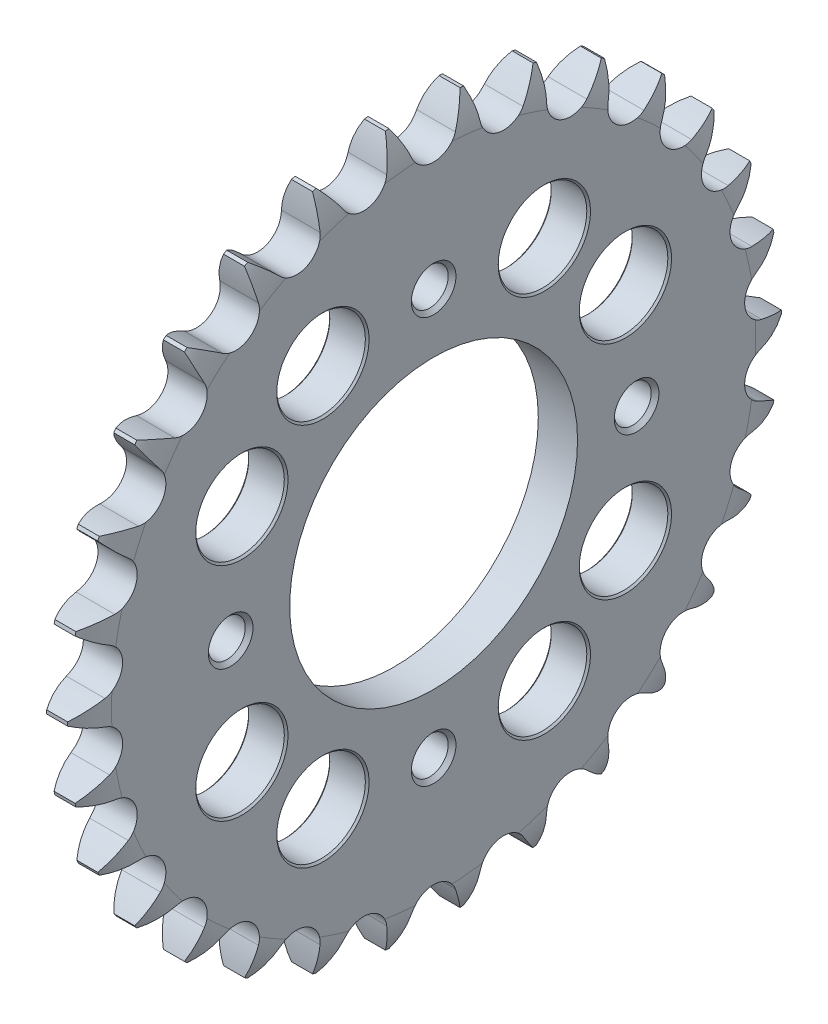
SolidWorks part; units mm, degrees
material "1.0503 (C45)"
ref_plane "Plane1" through (0, 0, 0) normal (0, 0, 1) x (1, 0, 0)
ref_plane "Plane2" through (0, 0, 0) normal (0, 1, 0) x (1, 0, 0)
ref_plane "Plane3" through (0, 0, 0) normal (1, 0, 0) x (0, 0, -1)
sketch "Clipboard" plane through (0, 0, 0) normal (0, 1, 0) x (1, 0, 0)
  line L0 (0, 0) -> (8.2489, -4.7625)
  line L1 (-15, 0) -> (100, 0) construction
  line L2 (0, 0) -> (-0.8203, 0.9272)
  line L3 (0, 0) -> (-8.8973, 3.4006)
  line L4 (0, 0) -> (2.6847, 1.55)
  line L5 (0, 0) -> (-46.8476, -17.4728)
  line L6 (0, 0) -> (-4.4098, -2.9753)
  line L7 (-0.8203, 0.9272) -> (42.0384, 26.6793)
  line L8 (-76.2, 38.1) -> (-75.5, 38.1)
  line L9 (-73.3242, 40.7328) -> (-72.926, 40.7699)
  line L10 (-73.4529, 9.1872) -> (-63.2129, 9.1872)
  circle A0 centre (0, 0) radius 3.175
  circle A1 centre (0, 0) radius 37.5
  circle A2 centre (0, 0) radius 37.5
  dimension "Dr" = 6.35
  dimension "MHD" = 75
  dimension "Hub_dia" = 75
  dimension "Num_teeth" = 30
  dimension "Pitch" = 9.525
  dimension "Width" = 3.1
  dimension "Side_relief" = 1.238
  dimension "Side_radius" = 9.525
  dimension "Overall_len" = 50
  dimension "Show_teeth" = 30
  dimension "Thickness" = 5.3196
  dimension "OAL" = 50.0005
  dimension "T_dim" = 0.7
  dimension "Fillet_rad" = 0.4
  dimension "Face_width" = 5.32
  dimension "Num_strands" = 1
  dimension "Transv_pitch" = 10.24
  dimension "Plate_wid" = 8.26
sketch "BasProSke" plane through (0, 0, 0) normal (0, 1, 0) x (1, 0, 0)
  line L0 (-10, 0) -> (60, 0) construction
  line L1 (0, 0) -> (0, 43.644)
  line L2 (0, 0) -> (5.3196, 0)
  line L3 (5.3196, 0) -> (5.3196, 43.644)
  line L4 (4.0816, 48.3399) -> (1.238, 48.3399)
  arc A0 (0, 43.644) -> (1.238, 48.3399) centre (9.525, 43.644) cw
  arc A1 (5.3196, 43.644) -> (4.0816, 48.3399) centre (-4.2054, 43.644) ccw
  dimension "Thickness" = 5.3196
  dimension "D1" = 9.525
  dimension "G1" = 1.238
  dimension "G2" = 1.238
  dimension "Diameter" = 96.6798
revolve "Base-Revolve" add sketch "BasProSke" angle 360 about L0
sketch "TooCutSke" plane through (0, 0, 0) normal (1, 0, 0) x (0, 0, -1)
  line L0 (0, 45.5935) -> (2.9836, 44.4182) construction
  line L1 (0, 0) -> (0, 107) construction
  line L2 (0, 45.5935) -> (-10, 45.5935) construction
  line L3 (0, 45.5935) -> (-2.9836, 44.4182) construction
  arc A0 (2.9836, 44.4182) -> (5.0993, 48.5729) centre (25.6709, 35.4815) cw
  arc A1 (2.9836, 44.4182) -> (-2.9836, 44.4182) centre (0, 45.5935) cw
  arc A2 (-2.9836, 44.4182) -> (-5.0993, 48.5729) centre (-25.6709, 35.4815) ccw
  arc A3 (5.0993, 48.5729) -> (-5.0993, 48.5729) centre (0, 0) ccw
  dimension "R1" = 3.2067
  dimension "R2" = 24.384
  dimension "Overcut" = 48.8399
  dimension "Seat_radius" = 45.5935
  dimension "X" = 137
extrude "ToothCut" cut sketch "TooCutSke" along normal through all
pattern_circular "TeethCuts" count 30 every 12 about axis through (-10, 0, 0) along (1, 0, 0) of "ToothCut"
sketch "HubNeaOneSke" plane through (0, 0, 0) normal (-1, 0, 0) x (0, 0, 1)
  circle A0 centre (0, 0) radius 37.5
  dimension "Diameter" = 75
extrude "HubNearOne" [suppressed] add sketch "HubNeaOneSke" along normal blind 44.6809
fillet "HubNearOneFillet" [suppressed] radius 0.4
sketch "HubNeaBotSke" plane through (0, 0, 0) normal (-1, 0, 0) x (0, 0, 1)
  circle A0 centre (0, 0) radius 37.5
  dimension "Diameter" = 75
extrude "HubNearBoth" [suppressed] add sketch "HubNeaBotSke" along normal blind 22.3405
fillet "HubNearBothFillet" [suppressed] radius 0.4
ref_plane "FarPln" through (5.3196, 0, 0) normal (1, 0, 0) x (0, 0, -1)
sketch "HubFarSke" plane through (5.3196, 0, 0) normal (1, 0, 0) x (0, 0, -1)
  circle A0 centre (0, 0) radius 37.5
  dimension "Diameter" = 75
extrude "HubFar" [suppressed] add sketch "HubFarSke" along normal blind 22.3405
fillet "HubFarFillet" [suppressed] radius 0.4
sketch "BorSke" plane through (0, 0, 0) normal (1, 0, 0) x (0, 0, -1)
  circle A0 centre (0, 0) radius 2
  dimension "Diameter" = 4
extrude "Bore" cut sketch "BorSke" along normal mid plane 100.001
sketch "KeySke" plane through (0, 0, 0) normal (1, 0, 0) x (0, 0, -1)
  line L0 (-0.8, 0) -> (-0.8, 2.7)
  line L1 (-0.8, 2.7) -> (0.8, 2.7)
  line L2 (0.8, 2.7) -> (0.8, 0)
  line L3 (0, 0) -> (0, 34) construction
  line L4 (-0.8, 0) -> (0.8, 0)
  dimension "Offset" = 2.7
  dimension "Width" = 1.6
extrude "Keyway" [suppressed] cut sketch "KeySke" along normal mid plane 100.001
pattern_circular "Keyway2" [suppressed] count 2 every 90 about axis through (-10, 0, 0) along (1, 0, 0)
sketch "Sketch1" plane through (5.3196, 0, 0) normal (1, 0, 0) x (0, 0, -1)
  circle A0 centre (0, 27.5) radius 3
  circle A1 centre (27.5, 0) radius 3
  circle A2 centre (0, -27.5) radius 3
  circle A3 centre (-27.5, 0) radius 3
  circle A4 centre (0, 0) radius 19.5
  point P11 (0, 0)
  dimension "D2" = 6
  dimension "D4" = 39
  dimension "D3" = 55
  dimension "D1" = 4
extrude "Cut-Extrude1" cut sketch "Sketch1" against normal blind 10 contours A4
hole_wizard "M6 Tapped Hole1" positions "Sketch3" profile "Sketch2" tap size "M6" standard "ISO" end condition through all
sketch "Sketch3" plane through (5.3196, 0, 0) normal (1, 0, 0) x (0, 0, -1)
  point P0 (0, 27.5)
  point P3 (-27.5, 0)
  point P6 (27.5, 0)
  point P9 (0, -27.5)
sketch "Sketch2" plane through (5.3196, 27.5, 0) normal (0, 1, 0) x (0, 0, -1)
  line L0 (0, 0) -> (0, 5.3196)
  line L1 (0, 5.3196) -> (2.5, 5.3196)
  line L2 (2.5, 5.3196) -> (2.5, 0.525)
  line L3 (2.5, 0.525) -> (3.025, 0)
  line L5 (3.025, 0) -> (0, 0)
  line L6 (-2.5, 0.525) -> (-3.025, 0) construction
  line L11 (0, -6.35) -> (0, 107.95) construction
  dimension "Thread Major Dia." = 5
  dimension "Thru Tap Drill Depth" = 5.3196
  dimension "Near C'Sink Dia." = 6.05
  dimension "Near C'Sink Angle" = 90
hole_wizard "Ø12.0 (12) Diameter Hole1" positions "Sketch7" profile "Sketch6" hole size "Ø12.0" standard "ISO" end condition through all
sketch "Sketch7" plane through (5.3196, 0, 0) normal (1, 0, 0) x (0, 0, -1)
  line L0 (0, 27.5) -> (0, 0) construction
  line L1 (0, 0) -> (15, 25.9808) construction
  point P0 (15, 25.9808)
  dimension "D1" = 30
  dimension "D2" = 30
sketch "Sketch6" plane through (5.3196, 25.9808, -15) normal (0, 1, 0) x (0, 0, -1)
  line L0 (0, 0) -> (0, 5.3196)
  line L1 (0, 5.3196) -> (6, 5.3196)
  line L2 (6, 5.3196) -> (6, 0)
  line L5 (6, 0) -> (0, 0)
  line L11 (0, -6.35) -> (0, 107.95) construction
  dimension "Thru Hole Dia." = 12
  dimension "Thru Hole Depth" = 5.3196
chamfer "Chamfer1" distance 0.25 angle 45 2 edges at (5.3196, 25.9808, -21) (0, 25.9808, -21)
pattern_circular "CirPattern1" count 12 over 360 about axis through (-4.6804, 0, 0) along (1, 0, 0) of "Ø12.0 (12) Diameter Hole1", "Chamfer1"
equation "' \"Pitch@Clipboard\" = 12.7"
equation "' \"Num_strands@Clipboard\" = 1"
equation "' \"Num_teeth@Clipboard\" = 9"
equation "' \"Hub_dia@Clipboard\" = 50"
equation "' \"Overall_len@Clipboard\" = 3"
equation "' \"Diameter@BorSke\" = 12"
equation "' \"T_dim@Clipboard\" = 1"
equation "' \"Width@KeySke\" = 2"
equation "' \"Dr@Clipboard\" = 8.51"
equation "' \"Face_width@Clipboard\" = 7.2"
equation "' \"Side_radius@Clipboard\" = 12.7"
equation "' \"Side_relief@Clipboard\" = 1.27"
equation "' \"Transv_pitch@Clipboard\" = 13.92"
equation "' \"Show_teeth@Clipboard\" = 9"
equation "' \"Fillet_rad@Clipboard\" = 0.6"
equation "' \"Plate_wid@Clipboard\" = 11.8"
equation "\"Num_teeth@Clipboard\" = int( \"Num_teeth@Clipboard\" )"
equation "\"Num_teeth@Clipboard\" = ((sgn( \"Num_teeth@Clipboard\" - 5.0)+1)*( \"Num_teeth@Clipboard\" - 5.0))/2 +5.0"
equation "\"Num_teeth@Clipboard\" = ((sgn( \"Num_teeth@Clipboard\" - 200.0)-1)*( \"Num_teeth@Clipboard\" - 200.0))/-2 +200.0"
equation "\"MHD@Clipboard\" = \"Pitch@Clipboard\" * (1.0 / tan(3.14159265 / \"Num_teeth@Clipboard\" )) - 1.04 * \"Plate_wid@Clipboard\" - 0.76"
equation "\"Thickness@Clipboard\"  = \"Face_width@Clipboard\" + (\"Num_strands@Clipboard\" - 1) * \"Transv_pitch@Clipboard\""
equation "\"OAL@Clipboard\" = \"Thickness@Clipboard\" + 2 * \"Fillet_rad@Clipboard\" + 1"
equation "\"MHD@Clipboard\" = ((sgn( \"MHD@Clipboard\" - \"Hub_dia@Clipboard\" )-1)*( \"MHD@Clipboard\" - \"Hub_dia@Clipboard\" ))/-2+ \"Hub_dia@Clipboard\""
equation "\"OAL@Clipboard\" = ((sgn( \"OAL@Clipboard\" - \"Overall_len@Clipboard\" )+1)*( \"OAL@Clipboard\" - \"Overall_len@Clipboard\" ))/2 + \"Overall_len@Clipboard\" + 0.0005"
equation "\"Num_teeth@TeethCuts\" = int( \"Show_teeth@Clipboard\" ) + 1"
equation "\"Num_teeth@TeethCuts\" = ((sgn( \"Num_teeth@TeethCuts\" - \"Num_teeth@Clipboard\" )-1)*( \"Num_teeth@TeethCuts\" - \"Num_teeth@Clipboard\" ))/-2+ \"Num_teeth@Clipboard\""
equation "\"Num_teeth@TeethCuts\" = ((sgn( \"Num_teeth@TeethCuts\" - 2.0)+1)*( \"Num_teeth@TeethCuts\" - 2.0))/2 +2.0"
equation "\"Angle@TeethCuts\" = 360.0 / \"Num_teeth@Clipboard\""
equation "\"Seat_radius@TooCutSke\" = ( \"Pitch@Clipboard\" / 2.0) / sin(3.14159265 / \"Num_teeth@Clipboard\" ) - \"Dr@Clipboard\" / 2.0 + \"Dr@Clipboard\" * 0.505"
equation "\"R1@TooCutSke\"  = \"Dr@Clipboard\" * 0.505"
equation "\"X@TooCutSke\" = 140.0 - (90.0 / \"Num_teeth@Clipboard\")"
equation "\"R2@TooCutSke\" = 0.12 * \"Dr@Clipboard\" * ( \"Num_teeth@Clipboard\" + 2.0)"
equation "\"Overcut@TooCutSke\" = 0.5 + 0.625 * \"Pitch@Clipboard\" - 0.5 * \"Dr@Clipboard\"  +  \"Pitch@Clipboard\" / 2.0 / sin(3.14159265 / \"Num_teeth@Clipboard\" )"
equation "\"Diameter@BasProSke\" = 2.0 * ( 0.625 * \"Pitch@Clipboard\" - 0.5 * \"Dr@Clipboard\"  +  \"Pitch@Clipboard\" / 2.0 / sin(3.14159265 / \"Num_teeth@Clipboard\" ))"
equation "\"Thickness@BasProSke\"  = \"Thickness@Clipboard\""
equation "\"G1@BasProSke\" =  \"Side_relief@Clipboard\""
equation "\"G2@BasProSke\" =  \"Side_relief@Clipboard\""
equation "\"D1@BasProSke\" =  \"Side_radius@Clipboard\""
equation "\"Diameter@HubNeaOneSke\" = \"MHD@Clipboard\""
equation "\"Length@HubNearOne\" = \"OAL@Clipboard\" - \"Thickness@BasProSke\""
equation "\"Diameter@HubNeaBotSke\" = \"MHD@Clipboard\""
equation "\"Length@HubNearBoth\" = ( \"OAL@Clipboard\" - \"Thickness@BasProSke\" ) / 2.0"
equation "\"D1@HubNearOneFillet\" = \"Fillet_rad@Clipboard\""
equation "\"D1@HubNearBothFillet\" = \"Fillet_rad@Clipboard\""
equation "\"Thickness@FarPln\" = \"Thickness@BasProSke\""
equation "\"Diameter@HubFarSke\" = \"MHD@Clipboard\""
equation "\"Length@HubFar\" = ( \"OAL@Clipboard\" - \"Thickness@BasProSke\" ) / 2.0"
equation "\"D1@HubFarFillet\" = \"Fillet_rad@Clipboard\""
equation "\"D1@Bore\" = \"OAL@Clipboard\" * 2.0"
equation "\"D1@Keyway\" = \"OAL@Clipboard\" * 2.0"
equation "\"Offset@KeySke\" = \"T_dim@Clipboard\" + \"Diameter@BorSke\" / 2.0"
